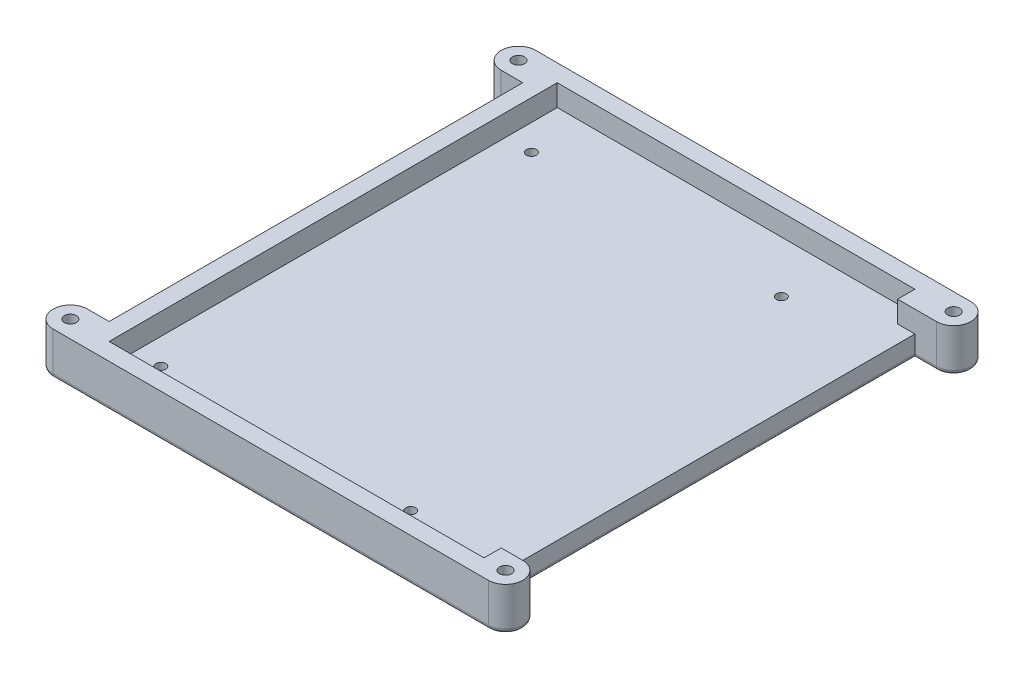
SolidWorks part; units mm, degrees
ref_plane "Front Plane" through (0, 0, 0) normal (0, 0, 1) x (1, 0, 0)
ref_plane "Top Plane" through (0, 0, 0) normal (0, 1, 0) x (1, 0, 0)
ref_plane "Right Plane" through (0, 0, 0) normal (1, 0, 0) x (0, 0, -1)
sketch "Sketch1" plane through (0, 0, 0) normal (0, 1, 0) x (1, 0, 0)
  line L0 (0, 56) -> (0, -56) construction
  line L1 (-39.5, 50) -> (39.5, 50) construction
  line L2 (-39.5, 50) -> (-39.5, -50) construction
  line L3 (-39.5, -50) -> (39.5, -50) construction
  line L4 (39.5, 50) -> (39.5, -50) construction
  line L5 (-45.5, 56) -> (45.5, 56)
  line L6 (-45.5, 56) -> (-45.5, -56)
  line L7 (-45.5, -56) -> (45.5, -56)
  line L8 (45.5, 56) -> (45.5, -56)
  circle A0 centre (-35.5, -46) radius 1.15
  circle A1 centre (22.5, -46) radius 1.15
  circle A2 centre (22.5, 40) radius 1.15
  circle A3 centre (-35.5, 40) radius 1.15
  point P4 (-39.5, 0)
  point P6 (0, 50)
  dimension "D5" = 2.3
  dimension "D6" = 86
  dimension "D7" = 58
  dimension "D8" = 4
  dimension "D9" = 4
  dimension "D1" = 79
  dimension "D2" = 100
  dimension "D3" = 112
  dimension "D4" = 91
extrude "Base" add sketch "Sketch1" along normal blind 10
sketch "Sketch2" plane through (0, 10, 0) normal (0, 1, 0) x (1, 0, 0)
  line L0 (0, 52) -> (0, -52) construction
  line L1 (-41.5, 52) -> (41.5, 52)
  line L2 (-41.5, 52) -> (-41.5, -52)
  line L3 (-41.5, -52) -> (41.5, -52)
  line L4 (41.5, 52) -> (41.5, -52)
  line L5 (-45.5, -56) -> (45.5, -56) construction
  line L6 (-45.5, 56) -> (-45.5, -56) construction
  dimension "D1" = 4
  dimension "D2" = 4
extrude "Module Cutout" cut sketch "Sketch2" against normal blind 5
sketch "Sketch3" plane through (0, 10, 0) normal (0, 1, 0) x (1, 0, 0)
  line L0 (-45.5, 56) -> (-50.5, 56)
  line L1 (-45.5, 56) -> (-45.5, -56) construction
  line L2 (-45.5, 56) -> (-45.5, 48)
  line L3 (-45.5, 48) -> (-50.5, 48)
  line L4 (45.5, 56) -> (-45.5, 56) construction
  line L5 (0, 56) -> (0, -56) construction
  line L6 (-45.5, -56) -> (45.5, -56) construction
  line L7 (45.5, 48) -> (50.5, 48)
  line L8 (45.5, 56) -> (45.5, 48)
  line L9 (45.5, 56) -> (50.5, 56)
  line L10 (-45.5, 0) -> (45.5, 0) construction
  line L11 (45.5, -56) -> (45.5, 56) construction
  line L12 (45.5, -56) -> (50.5, -56)
  line L13 (45.5, -56) -> (45.5, -48)
  line L14 (45.5, -48) -> (50.5, -48)
  line L15 (-45.5, -48) -> (-50.5, -48)
  line L16 (-45.5, -56) -> (-45.5, -48)
  line L17 (-45.5, -56) -> (-50.5, -56)
  arc A0 (-50.5, 48) -> (-50.5, 56) centre (-50.5, 52) cw
  circle A1 centre (-50.5, 52) radius 1.4
  circle A2 centre (50.5, 52) radius 1.4
  arc A3 (50.5, 48) -> (50.5, 56) centre (50.5, 52) ccw
  arc A4 (50.5, -48) -> (50.5, -56) centre (50.5, -52) cw
  circle A5 centre (50.5, -52) radius 1.4
  circle A6 centre (-50.5, -52) radius 1.4
  arc A7 (-50.5, -48) -> (-50.5, -56) centre (-50.5, -52) ccw
  dimension "D1" = 2.8
  dimension "D2" = 8
  dimension "D3" = 5
extrude "Case Assembly Holes" add sketch "Sketch3" against normal up to surface (10 mm away) up to face at (0, 0, 0)
sketch "Sketch5" plane through (0, 10, 0) normal (0, 1, 0) x (1, 0, 0)
  line L0 (41.5, -52) -> (41.5, 52) construction
  line L1 (41.5, 48) -> (45.5, 48)
  line L2 (41.5, 48) -> (41.5, -52)
  line L3 (41.5, -52) -> (45.5, -52)
  line L4 (45.5, 48) -> (45.5, -52)
  line L5 (-41.5, -52) -> (41.5, -52) construction
  line L6 (45.5, -48) -> (45.5, 48) construction
  line L7 (45.5, 48) -> (50.5, 48) construction
extrude "Ports Side Recess" cut sketch "Sketch5" against normal up to surface (5 mm away) up to face at (-35.5, 5, 47.15)
sketch "Sketch4" plane through (0, 0, 0) normal (0, -1, 0) x (1, 0, 0)
  line L0 (0, 25) -> (0, -25) construction
  line L1 (-15, 25) -> (15, 25) construction
  line L2 (-15, 25) -> (-15, -25) construction
  line L3 (-15, -25) -> (15, -25) construction
  line L4 (15, 25) -> (15, -25) construction
  circle A0 centre (-15, 25) radius 1.4
  circle A1 centre (-15, -25) radius 1.4
  circle A2 centre (15, -25) radius 1.4
  circle A3 centre (15, 25) radius 1.4
  point P7 (-15, 0)
  dimension "D3" = 2.8
  dimension "D1" = 30
  dimension "D2" = 50
extrude "Basket Clamp Mounting Holes" cut sketch "Sketch4" against normal blind 4
fillet "1mm Edge Fillets" radius 1 12 edges at (48, 0, 48) (-48, 0, 48) (-54.5, 0, 52) (0, 0, 56) (48, 0, -48) (54.5, 0, -52) (-48, 0, -48) (-54.5, 0, -52) (-45.5, 0, 0) (54.5, 0, 52) (45.5, 0, 0) (0, 0, -56)
